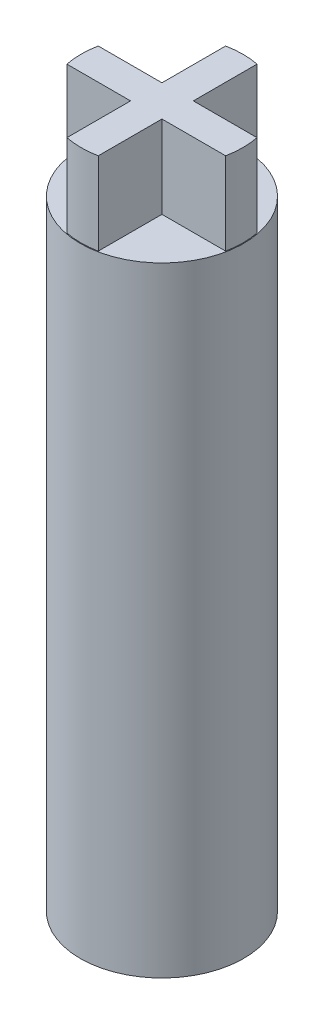
SolidWorks part; units mm, degrees
ref_plane "Front Plane" through (0, 0, 0) normal (0, 0, 1) x (1, 0, 0)
ref_plane "Top Plane" through (0, 0, 0) normal (0, 1, 0) x (1, 0, 0)
ref_plane "Right Plane" through (0, 0, 0) normal (1, 0, 0) x (0, 0, -1)
sketch "Sketch3" plane through (0, 0, 0) normal (0, 1, 0) x (1, 0, 0)
  circle A0 centre (0, 0) radius 9.9
  dimension "D1" = 19.8
extrude "Boss-Extrude1" add sketch "Sketch3" against normal blind 75
sketch "Sketch5" plane through (0, 0, 0) normal (0, 1, 0) x (1, 0, 0)
  line L14 (-2, 2) -> (-2, 9.6959)
  line L15 (2, 2) -> (2, 9.6959)
  line L16 (2, 2) -> (9.6959, 2)
  line L17 (2, -2) -> (9.6959, -2)
  line L18 (-2, 2) -> (-9.6959, 2)
  line L19 (-2, -2) -> (-9.6959, -2)
  line L20 (-2, -2) -> (-2, -9.6959)
  line L21 (2, -2) -> (2, -9.6959)
  circle A4 centre (0, 0) radius 9.9
ref_plane "Plane1" through (0, -75, 0) normal (0, -1, 0) x (-1, 0, 0)
sketch "Sketch7" plane through (0, -75, 0) normal (0, -1, 0) x (-1, 0, 0)
  line L1 (-2.16, 1.62) -> (2.16, 1.62)
  line L3 (-2.16, -1.62) -> (2.16, -1.62)
  line L8 (-1.62, 2.16) -> (-1.62, -2.16)
  line L10 (1.62, 2.16) -> (1.62, -2.16)
  circle A0 centre (0, 0) radius 2.7
  circle A1 centre (0, 0) radius 4.7
  dimension "D1" = 5.4
  dimension "D2" = 9.4
extrude "Cut-Extrude8" cut sketch "Sketch7" against normal blind 10.2 contours L8 A0 L10 L3 | L10 L1 L8 L3 | L10 A0 L8 L1 region at (0, -75, -2.0877) region at (0, -75, 0) region at (0, -75, 2.0877)
extrude "Cut-Extrude9" cut sketch "Sketch7<6>" against normal blind 4.2 contours L1 A0 L10 | L3 A0 L1 L10 | L10 A0 L3 | L3 A0 L8 | L1 A0 L3 L8 | L8 A0 L1 region at (1.8085, -75, -1.8085) region at (2.0877, -75, 0) region at (1.8085, -75, 1.8085) region at (-1.8085, -75, -1.8085) region at (-2.0877, -75, 0) region at (-1.8085, -75, 1.8085)
sketch "Sketch7<6>" plane through (0, -75, 0) normal (0, -1, 0) x (-1, 0, 0) same geometry as "Sketch7"
extrude "Cut-Extrude10" cut sketch "Sketch7<7>" against normal blind 2.2 contours A1 A0 region at (4.5671, -75, 0)
sketch "Sketch7<7>" plane through (0, -75, 0) normal (0, -1, 0) x (-1, 0, 0) same geometry as "Sketch7"
extrude "Boss-Extrude3" add sketch "Sketch5" along normal blind 10 contours L17 A4 L16 L15 L14 L18 L19 L20 L21 region at (0, 0, 0)
sketch "Sketch11" plane through (0, 10, 0) normal (0, 1, 0) x (1, 0, 0)
  line L1 (-1.9, 15.4601) -> (1.9, 15.4601)
  line L2 (-1.9, 15.4601) -> (-1.9, -15.4601)
  line L3 (-1.9, -15.4601) -> (1.9, -15.4601)
  line L4 (1.9, 15.4601) -> (1.9, -15.4601)
  line L5 (-1.9, 15.4601) -> (1.9, -15.4601) construction
  line L6 (-1.9, -15.4601) -> (1.9, 15.4601) construction
  line L7 (-12.5795, 1.9) -> (12.5795, 1.9)
  line L8 (-12.5795, 1.9) -> (-12.5795, -1.9)
  line L9 (-12.5795, -1.9) -> (12.5795, -1.9)
  line L10 (12.5795, 1.9) -> (12.5795, -1.9)
  line L11 (-12.5795, 1.9) -> (12.5795, -1.9) construction
  line L12 (-12.5795, -1.9) -> (12.5795, 1.9) construction
  circle A0 centre (0, 0) radius 9.9
  circle A1 centre (0, 0) radius 9.8
  point P0 (0, 0)
  line M10 (2, -2) -> (9.6959, -2)
  arc M11 (9.6959, -2) -> (9.6959, 2) centre (0, 0) ccw
  line M12 (9.6959, 2) -> (2, 2)
  line M13 (2, 2) -> (2, 9.6959)
  arc M14 (2, 9.6959) -> (-2, 9.6959) centre (0, 0) ccw
  line M15 (-2, 9.6959) -> (-2, 2)
  line M16 (-2, 2) -> (-9.6959, 2)
  arc M17 (-9.6959, 2) -> (-9.6959, -2) centre (0, 0) ccw
  line M18 (-9.6959, -2) -> (-2, -2)
  line M19 (-2, -2) -> (-2, -9.6959)
  arc M20 (-2, -9.6959) -> (2, -9.6959) centre (0, 0) ccw
  line M21 (2, -9.6959) -> (2, -2)
  dimension "D1" = 3.8
  dimension "D2" = 3.8
extrude "Cut-Extrude11" cut sketch "Sketch11" against normal blind 10 contours L2 A1 L7 M15 M16 | A1 L2 M14 M15 | A1 L4 L2 M14 | A1 L4 M13 M14 | L7 A1 L4 M12 M13 | A1 L7 M11 M12 | A1 L9 L7 M11 | A1 L9 M10 M11 | L4 A1 L9 M21 M10 | A1 L4 M20 M21 | A1 L2 L4 M20 | A1 L2 M19 M20 | L9 A1 L2 M18 M19 | A1 L7 M16 M17 | A1 L7 L9 M17 | A1 L9 M17 M18 region at (0, 10, -9.8619) region at (-1.95, 10, -9.655) region at (1.95, 10, -9.655) region at (-1.9109, 10, -5.757) region at (1.9283, 10, -9.4971) region at (-9.655, 10, -1.95) region at (9.655, 10, -1.95) region at (-1.9109, 10, 5.757) region at (-9.8381, 10, 0) region at (5.757, 10, 1.9109) region at (9.665, 10, -1.8619) region at (0, 10, 9.8381) region at (-1.95, 10, 9.655) region at (-9.655, 10, 1.95) region at (1.95, 10, 9.655) region at (9.655, 10, 1.95)
